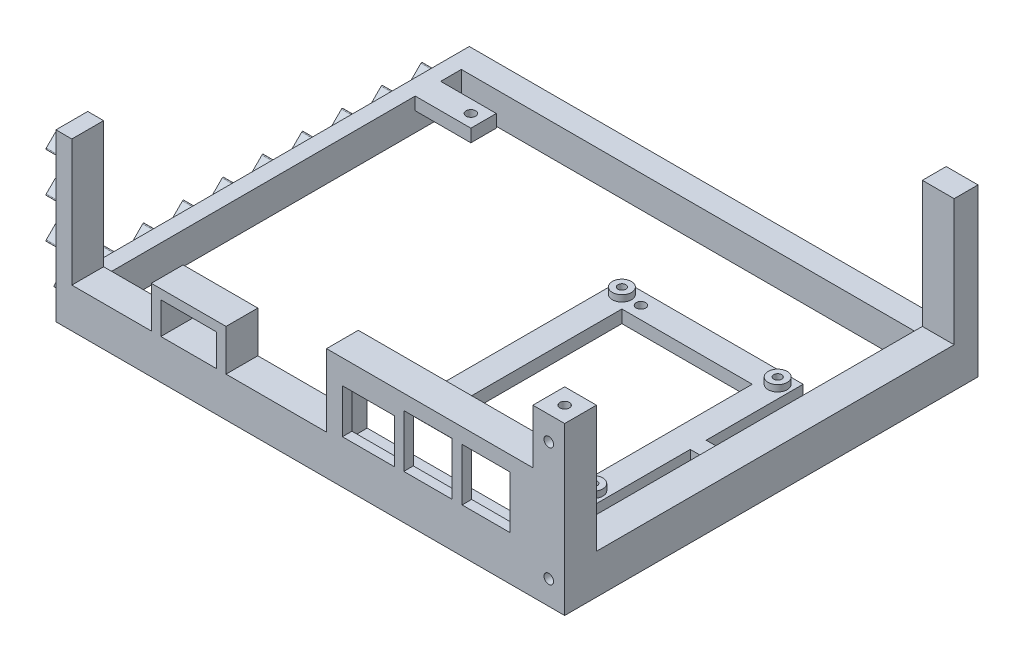
SolidWorks part; units mm, degrees
ref_plane "Front Plane" through (0, 0, 0) normal (0, 0, 1) x (1, 0, 0)
ref_plane "Top Plane" through (0, 0, 0) normal (0, 1, 0) x (1, 0, 0)
ref_plane "Right Plane" through (0, 0, 0) normal (1, 0, 0) x (0, 0, -1)
sketch "Sketch1" plane through (0, 0, 0) normal (0, 1, 0) x (1, 0, 0)
  line L0 (0, -65) -> (0, 65) construction
  line L1 (-75, -65) -> (85, -65)
  line L2 (-75, -65) -> (-75, 65)
  line L3 (-75, 65) -> (85, 65)
  line L4 (85, -65) -> (85, 65)
  point P0 (0, 0)
  point P9 (0, 0)
  dimension "D1" = 75
  dimension "D2" = 85
extrude "Boss-Extrude1" add sketch "Sketch1" along normal blind 10
sketch "Sketch3" plane through (0, 10, 0) normal (0, 1, 0) x (1, 0, 0)
  line L6 (85, 65) -> (-75, 65) construction
  line L9 (-75, 65) -> (-75, -65) construction
  line L10 (75, 65) -> (75, -55)
  line L13 (75, -55) -> (-75, -55)
  line L14 (-75, -55) -> (-75, -65)
  line L15 (-75, -65) -> (85, -65)
  line L16 (85, -65) -> (85, 65)
  line L17 (85, 65) -> (75, 65)
  dimension "D1" = 10
extrude "Boss-Extrude2" add sketch "Sketch3" along normal blind 42.3
sketch "Sketch8" plane through (0, 0, -65) normal (0, 0, -1) x (-1, 0, 0)
  line L0 (-75, 10) -> (-85, 10) construction
  line L56 (-85, 52.3) -> (-85, 0) construction
  line L57 (-75, 10) -> (-75, 0) construction
  line L59 (-85, 0) -> (75, 0) construction
  line L60 (-80, 10) -> (-80, 52.3) construction
  line L126 (-85, 52.3) -> (-75, 52.3) construction
  line L139 (-75, 5) -> (75, 5) construction
  line L140 (75, 10) -> (75, 0) construction
  line L141 (-83.425, 31.15) -> (-76.575, 31.15) construction
  line L142 (-83.425, 31.15) -> (-80, 34.575)
  line L143 (-80, 34.575) -> (-76.575, 31.15)
  line L144 (-76.575, 31.15) -> (-80, 27.725)
  line L145 (-80, 27.725) -> (-83.425, 31.15)
  line L146 (-80, 40.225) -> (-83.425, 43.65)
  line L147 (-83.425, 43.65) -> (-80, 47.075)
  line L148 (-80, 47.075) -> (-76.575, 43.65)
  line L149 (-76.575, 43.65) -> (-80, 40.225)
  line L150 (-80, 15.225) -> (-83.425, 18.65)
  line L151 (-83.425, 18.65) -> (-80, 22.075)
  line L152 (-80, 22.075) -> (-76.575, 18.65)
  line L153 (-76.575, 18.65) -> (-80, 15.225)
  line L154 (0, 1.575) -> (0, 8.425) construction
  line L155 (0, 8.425) -> (-3.425, 5)
  line L156 (-3.425, 5) -> (0, 1.575)
  line L157 (0, 1.575) -> (3.425, 5)
  line L158 (3.425, 5) -> (0, 8.425)
  line L159 (15.925, 5) -> (12.5, 8.425)
  line L160 (12.5, 8.425) -> (9.075, 5)
  line L161 (9.075, 5) -> (12.5, 1.575)
  line L162 (12.5, 1.575) -> (15.925, 5)
  line L163 (28.425, 5) -> (25, 8.425)
  line L164 (25, 8.425) -> (21.575, 5)
  line L165 (21.575, 5) -> (25, 1.575)
  line L166 (25, 1.575) -> (28.425, 5)
  line L167 (40.925, 5) -> (37.5, 8.425)
  line L168 (37.5, 8.425) -> (34.075, 5)
  line L169 (34.075, 5) -> (37.5, 1.575)
  line L170 (37.5, 1.575) -> (40.925, 5)
  line L171 (53.425, 5) -> (50, 8.425)
  line L172 (50, 8.425) -> (46.575, 5)
  line L173 (46.575, 5) -> (50, 1.575)
  line L174 (50, 1.575) -> (53.425, 5)
  line L175 (65.925, 5) -> (62.5, 8.425)
  line L176 (62.5, 8.425) -> (59.075, 5)
  line L177 (59.075, 5) -> (62.5, 1.575)
  line L178 (62.5, 1.575) -> (65.925, 5)
  line L179 (-9.075, 5) -> (-12.5, 8.425)
  line L180 (-12.5, 8.425) -> (-15.925, 5)
  line L181 (-15.925, 5) -> (-12.5, 1.575)
  line L182 (-12.5, 1.575) -> (-9.075, 5)
  line L183 (-21.575, 5) -> (-25, 8.425)
  line L184 (-25, 8.425) -> (-28.425, 5)
  line L185 (-28.425, 5) -> (-25, 1.575)
  line L186 (-25, 1.575) -> (-21.575, 5)
  line L187 (-34.075, 5) -> (-37.5, 8.425)
  line L188 (-37.5, 8.425) -> (-40.925, 5)
  line L189 (-40.925, 5) -> (-37.5, 1.575)
  line L190 (-37.5, 1.575) -> (-34.075, 5)
  line L191 (-46.575, 5) -> (-50, 8.425)
  line L192 (-50, 8.425) -> (-53.425, 5)
  line L193 (-53.425, 5) -> (-50, 1.575)
  line L194 (-50, 1.575) -> (-46.575, 5)
  line L195 (-59.075, 5) -> (-62.5, 8.425)
  line L196 (-62.5, 8.425) -> (-65.925, 5)
  line L197 (-65.925, 5) -> (-62.5, 1.575)
  line L198 (-62.5, 1.575) -> (-59.075, 5)
  line L199 (-71.575, 5) -> (-75, 8.425)
  line L200 (-75, 8.425) -> (-78.425, 5)
  line L201 (-78.425, 5) -> (-75, 1.575)
  line L202 (-75, 1.575) -> (-71.575, 5)
  point P18 (-80, 31.15)
  point P31 (0, 5)
  dimension "D1" = 2
  dimension "D2" = 2
extrude "Cut-Extrude3" cut sketch "Sketch8" against normal blind 5.25
sketch "Sketch9" plane through (0, 10, 0) normal (0, 1, 0) x (1, 0, 0)
  line L1 (-75, 65) -> (-75, -55) construction
  line L5 (-70, -55) -> (75, -55)
  line L6 (-70, 51) -> (-70, 57.5)
  line L7 (-70, 43) -> (-70, -55)
  line L8 (75, -55) -> (75, 57.5)
  line L9 (75, 65) -> (75, -55) construction
  line L10 (75, 57.5) -> (-70, 57.5)
  line L12 (75, 65) -> (-75, 65) construction
  line L13 (-52.5, 47) -> (-56.5, 47) construction
  line L14 (-70, 43) -> (-52.5, 43)
  line L15 (-52.5, 43) -> (-52.5, 51)
  line L16 (-52.5, 51) -> (-70, 51)
  circle A1 centre (-56.5, 47) radius 1.5
  dimension "D4" = 5
  dimension "D1" = 7.5
  dimension "D5" = 17.5
extrude "Cut-Extrude4" cut sketch "Sketch9" against normal through all
sketch "Sketch10" plane through (-75, 0, 0) normal (-1, 0, 0) x (0, 0, 1)
  line L0 (55, 10) -> (65, 10) construction
  line L1 (10.5379, 5.2121) -> (7.7121, 8.0379)
  line L2 (7.2879, 8.0379) -> (4.4621, 5.2121)
  line L40 (65, 52.3) -> (65, 0) construction
  line L41 (55, 10) -> (55, 0) construction
  line L42 (-65, 0) -> (65, 0) construction
  line L43 (4.4621, 4.7879) -> (7.2879, 1.9621)
  line L57 (60, 10) -> (60, 52.3) construction
  line L94 (55, 52.3) -> (65, 52.3) construction
  line L111 (63.25, 31.15) -> (56.75, 31.15) construction
  line L112 (56.9621, 31.3621) -> (59.7879, 34.1879)
  line L113 (60.2121, 34.1879) -> (63.0379, 31.3621)
  line L114 (63.0379, 30.9379) -> (60.2121, 28.1121)
  line L115 (59.7879, 28.1121) -> (56.9621, 30.9379)
  line L124 (55, 5) -> (-65, 5) construction
  line L125 (-65, 10) -> (-65, 0) construction
  line L126 (-5, 8.25) -> (-5, 1.75) construction
  line L127 (-5.2121, 8.0379) -> (-8.0379, 5.2121)
  line L128 (-8.0379, 4.7879) -> (-5.2121, 1.9621)
  line L129 (-4.7879, 1.9621) -> (-1.9621, 4.7879)
  line L130 (-1.9621, 5.2121) -> (-4.7879, 8.0379)
  line L131 (59.7879, 40.6121) -> (56.9621, 43.4379)
  line L132 (56.9621, 43.8621) -> (59.7879, 46.6879)
  line L133 (60.2121, 46.6879) -> (63.0379, 43.8621)
  line L134 (63.0379, 43.4379) -> (60.2121, 40.6121)
  line L135 (59.7879, 15.6121) -> (56.9621, 18.4379)
  line L136 (56.9621, 18.8621) -> (59.7879, 21.6879)
  line L137 (60.2121, 21.6879) -> (63.0379, 18.8621)
  line L138 (63.0379, 18.4379) -> (60.2121, 15.6121)
  line L139 (7.7121, 1.9621) -> (10.5379, 4.7879)
  line L140 (23.0379, 5.2121) -> (20.2121, 8.0379)
  line L141 (19.7879, 8.0379) -> (16.9621, 5.2121)
  line L142 (16.9621, 4.7879) -> (19.7879, 1.9621)
  line L143 (20.2121, 1.9621) -> (23.0379, 4.7879)
  line L144 (35.5379, 5.2121) -> (32.7121, 8.0379)
  line L145 (32.2879, 8.0379) -> (29.4621, 5.2121)
  line L146 (29.4621, 4.7879) -> (32.2879, 1.9621)
  line L147 (32.7121, 1.9621) -> (35.5379, 4.7879)
  line L148 (48.0379, 5.2121) -> (45.2121, 8.0379)
  line L149 (44.7879, 8.0379) -> (41.9621, 5.2121)
  line L150 (41.9621, 4.7879) -> (44.7879, 1.9621)
  line L151 (45.2121, 1.9621) -> (48.0379, 4.7879)
  line L152 (60.5379, 5.2121) -> (57.7121, 8.0379)
  line L153 (57.2879, 8.0379) -> (54.4621, 5.2121)
  line L154 (54.4621, 4.7879) -> (57.2879, 1.9621)
  line L155 (57.7121, 1.9621) -> (60.5379, 4.7879)
  line L156 (-14.4621, 5.2121) -> (-17.2879, 8.0379)
  line L157 (-17.7121, 8.0379) -> (-20.5379, 5.2121)
  line L158 (-20.5379, 4.7879) -> (-17.7121, 1.9621)
  line L159 (-17.2879, 1.9621) -> (-14.4621, 4.7879)
  line L160 (-26.9621, 5.2121) -> (-29.7879, 8.0379)
  line L161 (-30.2121, 8.0379) -> (-33.0379, 5.2121)
  line L162 (-33.0379, 4.7879) -> (-30.2121, 1.9621)
  line L163 (-29.7879, 1.9621) -> (-26.9621, 4.7879)
  line L164 (-39.4621, 5.2121) -> (-42.2879, 8.0379)
  line L165 (-42.7121, 8.0379) -> (-45.5379, 5.2121)
  line L166 (-45.5379, 4.7879) -> (-42.7121, 1.9621)
  line L167 (-42.2879, 1.9621) -> (-39.4621, 4.7879)
  line L168 (-51.9621, 5.2121) -> (-54.7879, 8.0379)
  line L169 (-55.2121, 8.0379) -> (-58.0379, 5.2121)
  line L170 (-58.0379, 4.7879) -> (-55.2121, 1.9621)
  line L171 (-54.7879, 1.9621) -> (-51.9621, 4.7879)
  arc A100 (-4.7879, 1.9621) -> (-5.2121, 1.9621) centre (-5, 2.1743) cw
  arc A101 (-8.0379, 5.2121) -> (-8.0379, 4.7879) centre (-7.8257, 5) ccw
  arc A102 (-1.9621, 4.7879) -> (-1.9621, 5.2121) centre (-2.1743, 5) ccw
  arc A103 (-4.7879, 8.0379) -> (-5.2121, 8.0379) centre (-5, 7.8257) ccw
  arc A104 (56.9621, 30.9379) -> (56.9621, 31.3621) centre (57.1743, 31.15) cw
  arc A105 (60.2121, 28.1121) -> (59.7879, 28.1121) centre (60, 28.3243) cw
  arc A106 (63.0379, 30.9379) -> (63.0379, 31.3621) centre (62.8257, 31.15) ccw
  arc A107 (59.7879, 34.1879) -> (60.2121, 34.1879) centre (60, 33.9757) cw
  arc A108 (60.2121, 40.6121) -> (59.7879, 40.6121) centre (60, 40.8243) cw
  arc A109 (56.9621, 43.4379) -> (56.9621, 43.8621) centre (57.1743, 43.65) cw
  arc A110 (59.7879, 46.6879) -> (60.2121, 46.6879) centre (60, 46.4757) cw
  arc A111 (63.0379, 43.4379) -> (63.0379, 43.8621) centre (62.8257, 43.65) ccw
  arc A112 (60.2121, 15.6121) -> (59.7879, 15.6121) centre (60, 15.8243) cw
  arc A113 (56.9621, 18.4379) -> (56.9621, 18.8621) centre (57.1743, 18.65) cw
  arc A114 (59.7879, 21.6879) -> (60.2121, 21.6879) centre (60, 21.4757) cw
  arc A115 (63.0379, 18.4379) -> (63.0379, 18.8621) centre (62.8257, 18.65) ccw
  arc A116 (7.7121, 8.0379) -> (7.2879, 8.0379) centre (7.5, 7.8257) ccw
  arc A117 (10.5379, 4.7879) -> (10.5379, 5.2121) centre (10.3257, 5) ccw
  arc A118 (4.4621, 5.2121) -> (4.4621, 4.7879) centre (4.6743, 5) ccw
  arc A119 (7.7121, 1.9621) -> (7.2879, 1.9621) centre (7.5, 2.1743) cw
  arc A120 (20.2121, 8.0379) -> (19.7879, 8.0379) centre (20, 7.8257) ccw
  arc A121 (23.0379, 4.7879) -> (23.0379, 5.2121) centre (22.8257, 5) ccw
  arc A122 (16.9621, 5.2121) -> (16.9621, 4.7879) centre (17.1743, 5) ccw
  arc A123 (20.2121, 1.9621) -> (19.7879, 1.9621) centre (20, 2.1743) cw
  arc A124 (32.7121, 8.0379) -> (32.2879, 8.0379) centre (32.5, 7.8257) ccw
  arc A125 (35.5379, 4.7879) -> (35.5379, 5.2121) centre (35.3257, 5) ccw
  arc A126 (29.4621, 5.2121) -> (29.4621, 4.7879) centre (29.6743, 5) ccw
  arc A127 (32.7121, 1.9621) -> (32.2879, 1.9621) centre (32.5, 2.1743) cw
  arc A128 (45.2121, 8.0379) -> (44.7879, 8.0379) centre (45, 7.8257) ccw
  arc A129 (48.0379, 4.7879) -> (48.0379, 5.2121) centre (47.8257, 5) ccw
  arc A130 (41.9621, 5.2121) -> (41.9621, 4.7879) centre (42.1743, 5) ccw
  arc A131 (45.2121, 1.9621) -> (44.7879, 1.9621) centre (45, 2.1743) cw
  arc A132 (57.7121, 8.0379) -> (57.2879, 8.0379) centre (57.5, 7.8257) ccw
  arc A133 (60.5379, 4.7879) -> (60.5379, 5.2121) centre (60.3257, 5) ccw
  arc A134 (54.4621, 5.2121) -> (54.4621, 4.7879) centre (54.6743, 5) ccw
  arc A135 (57.7121, 1.9621) -> (57.2879, 1.9621) centre (57.5, 2.1743) cw
  arc A136 (-17.2879, 8.0379) -> (-17.7121, 8.0379) centre (-17.5, 7.8257) ccw
  arc A137 (-14.4621, 4.7879) -> (-14.4621, 5.2121) centre (-14.6743, 5) ccw
  arc A138 (-20.5379, 5.2121) -> (-20.5379, 4.7879) centre (-20.3257, 5) ccw
  arc A139 (-17.2879, 1.9621) -> (-17.7121, 1.9621) centre (-17.5, 2.1743) cw
  arc A140 (-29.7879, 8.0379) -> (-30.2121, 8.0379) centre (-30, 7.8257) ccw
  arc A141 (-26.9621, 4.7879) -> (-26.9621, 5.2121) centre (-27.1743, 5) ccw
  arc A142 (-33.0379, 5.2121) -> (-33.0379, 4.7879) centre (-32.8257, 5) ccw
  arc A143 (-29.7879, 1.9621) -> (-30.2121, 1.9621) centre (-30, 2.1743) cw
  arc A144 (-42.2879, 8.0379) -> (-42.7121, 8.0379) centre (-42.5, 7.8257) ccw
  arc A145 (-39.4621, 4.7879) -> (-39.4621, 5.2121) centre (-39.6743, 5) ccw
  arc A146 (-45.5379, 5.2121) -> (-45.5379, 4.7879) centre (-45.3257, 5) ccw
  arc A147 (-42.2879, 1.9621) -> (-42.7121, 1.9621) centre (-42.5, 2.1743) cw
  arc A148 (-54.7879, 8.0379) -> (-55.2121, 8.0379) centre (-55, 7.8257) ccw
  arc A149 (-51.9621, 4.7879) -> (-51.9621, 5.2121) centre (-52.1743, 5) ccw
  arc A150 (-58.0379, 5.2121) -> (-58.0379, 4.7879) centre (-57.8257, 5) ccw
  arc A151 (-54.7879, 1.9621) -> (-55.2121, 1.9621) centre (-55, 2.1743) cw
  point P14 (60, 31.15)
  point P23 (-8.25, 5)
  point P31 (-5, 5)
  point P32 (-1.75, 5)
  point P42 (60, 27.9)
  point P48 (60, 34.4)
  dimension "D1" = 0.3
  dimension "D3" = 2
  dimension "D2" = 2
sketch "Sketch11" plane through (75, 0, 0) normal (-1, 0, 0) x (0, 0, 1)
  line L1 (-65, 52.3) -> (55, 52.3) construction
  line L2 (-57.5, 52.3) -> (55, 52.3)
  line L6 (-57.5, 52.3) -> (-57.5, 12.5)
  line L7 (-57.5, 12.5) -> (55, 12.5)
  line L8 (55, 52.3) -> (55, 0) construction
  line L9 (55, 12.5) -> (55, 52.3)
  line L10 (55, 0) -> (-57.5, 0) construction
  dimension "D1" = 12.5
extrude "Cut-Extrude5" cut sketch "Sketch11" against normal through all
sketch "Sketch14" plane through (0, 0, 0) normal (0, 1, 0) x (1, 0, 0)
  line L0 (65.5, -36.5) -> (75, -36.5) construction
  line L1 (49.5, -7.5) -> (75.0071, -7.5) construction
  line L2 (65.5, -36.5) -> (65.5, -55) construction
  line L3 (75, -55) -> (75, 57.5) construction
  line L4 (75, 57.5) -> (75, -55) construction
  line L5 (65.5, -36.5) -> (16.5, -36.5) construction
  line L6 (16.5, -36.5) -> (16.5, 21.5) construction
  line L7 (16.5, 21.5) -> (65.5, 21.5) construction
  line L8 (65.5, 21.5) -> (65.5, -36.5) construction
  line L9 (41, -36.5) -> (41, 21.5) construction
  line L10 (16.5, -7.5) -> (65.5, -7.5) construction
  line L11 (58.5002, -55) -> (23.4998, -55)
  line L12 (61.5, 17.5) -> (20.5, 17.5)
  line L13 (61.5, 17.5) -> (61.5, -32.5)
  line L14 (61.5, -32.5) -> (20.5, -32.5)
  line L15 (20.5, 17.5) -> (20.5, -32.5)
  line L16 (69.5, 25.5) -> (12.5, 25.5)
  line L17 (69.5, 25.5) -> (69.5, -5)
  line L18 (69.5, -40.5) -> (23.4998, -40.5)
  line L19 (12.5, 25.5) -> (12.5, -40.5)
  line L20 (58.5002, -55) -> (58.5002, -40.5)
  line L22 (58.5002, -40.5) -> (12.5, -40.5)
  line L23 (75.0142, -5) -> (75, -10)
  line L24 (75.0142, -5) -> (69.5, -5)
  line L25 (75, -10) -> (69.5, -10)
  line L26 (69.5, -10) -> (69.5, -40.5)
  line L27 (41, -36.5) -> (41, -55) construction
  line L28 (-70, -55) -> (75, -55) construction
  line L29 (23.4998, -40.5) -> (23.4998, -55)
  circle A0 centre (65.5, -36.5) radius 1.25
  circle A1 centre (16.5, -36.5) radius 1.25
  circle A2 centre (16.5, 21.5) radius 1.25
  circle A3 centre (65.5, 21.5) radius 1.25
  circle A4 centre (22.5, 21.5) radius 1.5
  circle A5 centre (59.5, -36.5) radius 1.5
  circle A6 centre (16.5, -36.5) radius 3
  circle A7 centre (65.5, -36.5) radius 3
  circle A8 centre (16.5, 21.5) radius 3
  circle A9 centre (65.5, 21.5) radius 3
  point P26 (41, -7.5)
  point P31 (41, -7.5)
  point P41 (41, -55)
  point P46 (75.0071, -7.5)
  dimension "D1" = 6
  dimension "D3" = 4
  dimension "D2" = 6
  dimension "D4" = 4
  dimension "D5" = 4
  dimension "D6" = 4
  dimension "D7" = 58
  dimension "D8" = 49
  dimension "D9" = 4
  dimension "D10" = 4
  dimension "D11" = 4
  dimension "D12" = 4
  dimension "D13" = 5.5
extrude "Boss-Extrude7" add sketch "Sketch14" along normal blind 10 contours L26 L25 L23 L24 L17 L16 L19 L22 L20 L11 L29 L18 A9 A8 A7 A6 A5 A4 L15 L12 L13 L14 | A7 A0 | A6 A1 | A8 A2 | A9 A3 region at (41, 0, 39.5909) region at (13.5849, 0, 36.5) region at (62.5849, 0, 36.5) region at (13.5849, 0, -21.5) region at (62.5849, 0, -21.5)
extrude "Boss-Extrude8" add sketch "Sketch14<3>" along normal blind 12 contours A8 A2 | A9 A3 | A7 A0 | A6 A1 region at (13.5849, 0, 36.5) region at (62.5849, 0, 36.5) region at (13.5849, 0, -21.5) region at (62.5849, 0, -21.5)
sketch "Sketch14<3>" plane through (0, 0, 0) normal (0, 1, 0) x (1, 0, 0) same geometry as "Sketch14"
sketch "Sketch15" plane through (0, 52.3, 0) normal (0, 1, 0) x (1, 0, 0)
  line L0 (80, -60) -> (85, -60) construction
  line L2 (85, -65) -> (85, -55) construction
  line L3 (80, -60) -> (80, -65) construction
  line L4 (-75, -65) -> (85, -65) construction
  circle A0 centre (80, -60) radius 1.5
extrude "Cut-Extrude7" cut sketch "Sketch15" against normal blind 4
sketch "Sketch16" plane through (0, 0, 0) normal (0, -1, 0) x (1, 0, 0)
  circle A0 centre (80, 60) radius 1.5 construction
  circle A1 centre (80, 60) radius 1.5
extrude "Cut-Extrude8" cut sketch "Sketch16" against normal blind 4
sketch "Sketch17" plane through (0, 0, 0) normal (0, -1, 0) x (1, 0, 0)
  line L4 (-70, -43) -> (-70, -51)
  line L5 (-70, -51) -> (-52.5, -51)
  line L6 (-52.5, -51) -> (-52.5, -43)
  line L7 (-52.5, -43) -> (-70, -43)
extrude "Cut-Extrude9" cut sketch "Sketch17" against normal blind 6
sketch "Sketch18" plane through (0, 0, 0) normal (0, -1, 0) x (1, 0, 0)
  line L0 (12.5, -25.5) -> (12.5, 55)
  line L1 (-70, 55) -> (75, 55) construction
  line L2 (12.5, 55) -> (75, 55)
  line L3 (12.5, -25.5) -> (75, -25.5)
  line L5 (75, 5) -> (75, -57.5) construction
  line L6 (75, -25.5) -> (75, 55)
extrude "Cut-Extrude10" cut sketch "Sketch18" against normal blind 6
sketch "Sketch19" plane through (0, 0, 65) normal (0, 0, 1) x (1, 0, 0)
  line L0 (80, 7.5) -> (85, 7.5) construction
  line L1 (85, 52.3) -> (85, 0) construction
  line L2 (80, 7.5) -> (80, 0) construction
  line L4 (80, 44.8) -> (85, 44.8) construction
  line L6 (80, 44.8) -> (80, 52.3) construction
  line L7 (-75, 0) -> (85, 0) construction
  line L9 (-75, 52.3) -> (85, 52.3) construction
  circle A0 centre (80, 7.5) radius 1.5
  circle A1 centre (80, 44.8) radius 1.5
extrude "Cut-Extrude11" cut sketch "Sketch19" against normal blind 4
sketch "Sketch21" plane through (0, 0, 65) normal (0, 0, 1) x (1, 0, 0)
  line L4 (-75, 52.3) -> (-75, 0) construction
  line L19 (-70, 12.5) -> (-70, 52.3)
  line L20 (-70, 52.3) -> (75, 52.3)
  line L24 (-75, 0) -> (85, 0) construction
  line L26 (-45, 12.5) -> (-70, 12.5)
  line L28 (85, 52.3) -> (85, 0) construction
  line L29 (85, 12.5) -> (85, 52.3)
  line L38 (-33.25, 25.5) -> (-33.25, 12.5) construction
  line L40 (15.1, 27.65) -> (15.1, 13.75)
  line L41 (-45, 25.5) -> (-45, 12.5)
  line L44 (15.1, 13.75) -> (31.5, 13.75)
  line L45 (31.5, 13.75) -> (31.5, 27.65)
  line L46 (31.5, 27.65) -> (15.1, 27.65)
  line L47 (34.4, 13.9581) -> (34.4, 30.5419)
  line L48 (34.4, 30.5419) -> (49.6, 30.5419)
  line L49 (49.6, 30.5419) -> (49.6, 13.9581)
  line L50 (49.6, 13.9581) -> (34.4, 13.9581)
  line L54 (52.75, 13.9991) -> (52.75, 30.5009)
  line L55 (12.9, 32.25) -> (69.9, 32.25)
  line L57 (69.9, 32.25) -> (69.9, 10)
  line L58 (69.9, 12.5) -> (75, 12.5)
  line L59 (69.9, 10) -> (12.9, 10)
  line L60 (12.9, 10) -> (12.9, 32.25)
  line L61 (29, 35.25) -> (29, 12.5) construction
  line L62 (10.1, 25.5) -> (10.1, 35.25)
  line L63 (29, 35.25) -> (75, 35.25)
  line L64 (10.1, 35.25) -> (29, 35.25)
  line L65 (75, 52.3) -> (75, 0)
  line L66 (75, 0) -> (-70, 0)
  line L67 (-70, 0) -> (-70, 12.5)
  line L68 (-70, 12.5) -> (-70, 0)
  line L70 (67.75, 30.5009) -> (67.75, 13.9991)
  line L72 (52.75, 30.5009) -> (67.75, 30.5009)
  line L73 (67.75, 13.9991) -> (52.75, 13.9991)
  line L74 (15.1, 27.65) -> (31.5, 13.75) construction
  line L75 (15.1, 13.75) -> (31.5, 27.65) construction
  line L76 (34.4, 30.5419) -> (49.6, 13.9581) construction
  line L77 (34.4, 13.9581) -> (49.6, 30.5419) construction
  line L78 (52.75, 30.5009) -> (67.75, 13.9991) construction
  line L79 (52.75, 13.9991) -> (67.75, 30.5009) construction
  line L80 (23.3, 20.7) -> (23.3, 35.25) construction
  line L81 (42, 22.25) -> (42, 35.25) construction
  line L82 (60.25, 22.25) -> (60.25, 35.25) construction
  line L83 (10.1, 25.5) -> (10.1, 12.5)
  line L84 (10.1, 12.5) -> (69.9, 12.5) construction
  line L85 (-21.5, 12.5) -> (-21.5, 25.5)
  line L86 (10.1, 12.5) -> (-21.5, 12.5)
  line L87 (-42, 22.5) -> (-42, 12.5)
  line L88 (-42, 12.5) -> (-24.5, 12.5)
  line L89 (-24.5, 22.5) -> (-24.5, 12.5)
  line L90 (-42, 22.5) -> (-24.5, 22.5)
  line L91 (-45, 25.5) -> (-21.5, 25.5)
  line M21 (85, 52.3) -> (-75, 52.3)
  dimension "D2" = 10
  dimension "D3" = 2.8
  dimension "D4" = 3
  dimension "D5" = 10
  dimension "D1" = 5
  dimension "D6" = 12.5
  dimension "D7" = 3
  dimension "D8" = 12.5
  dimension "D9" = 12.5
  dimension "D10" = 17.5
  dimension "D11" = 13.9
  dimension "D12" = 16.5838
  dimension "D13" = 16.5018
  dimension "D14" = 16.4
  dimension "D15" = 15.2
  dimension "D16" = 15
  dimension "D17" = 43.35
  dimension "D18" = 3
extrude "Cut-Extrude14" cut sketch "Sketch21" against normal blind 10 contours L65 L19 L26 L41 L62 L64 L61 L58 M21 | L91 | L45 L46 L40 L44 | L50 L49 L48 L47 | L54 | L90 L87 L88 L89 region at (-9.586, 36.5816, 65) region at (23.3, 20.7, 65) region at (42, 22.25, 65) region at (60.25, 22.25, 65) region at (-33.25, 17.5, 65)
sketch "Sketch22" plane through (0, 0, 55) normal (0, 0, -1) x (-1, 0, 0)
  line L0 (-69.9, 32.25) -> (-69.9, 10) construction
  line L1 (-69.9, 10) -> (-12.9, 10) construction
  line L2 (-12.9, 10) -> (-12.9, 32.25) construction
  line L3 (-12.9, 32.25) -> (-69.9, 32.25) construction
  line L4 (-69.9, 32.25) -> (-69.9, 10)
  line L5 (-69.9, 10) -> (-12.9, 10)
  line L6 (-12.9, 10) -> (-12.9, 32.25)
  line L7 (-12.9, 32.25) -> (-69.9, 32.25)
extrude "Cut-Extrude16" cut sketch "Sketch22" against normal blind 7
extrude "Boss-Extrude9" add sketch "Sketch10" along normal blind 5
